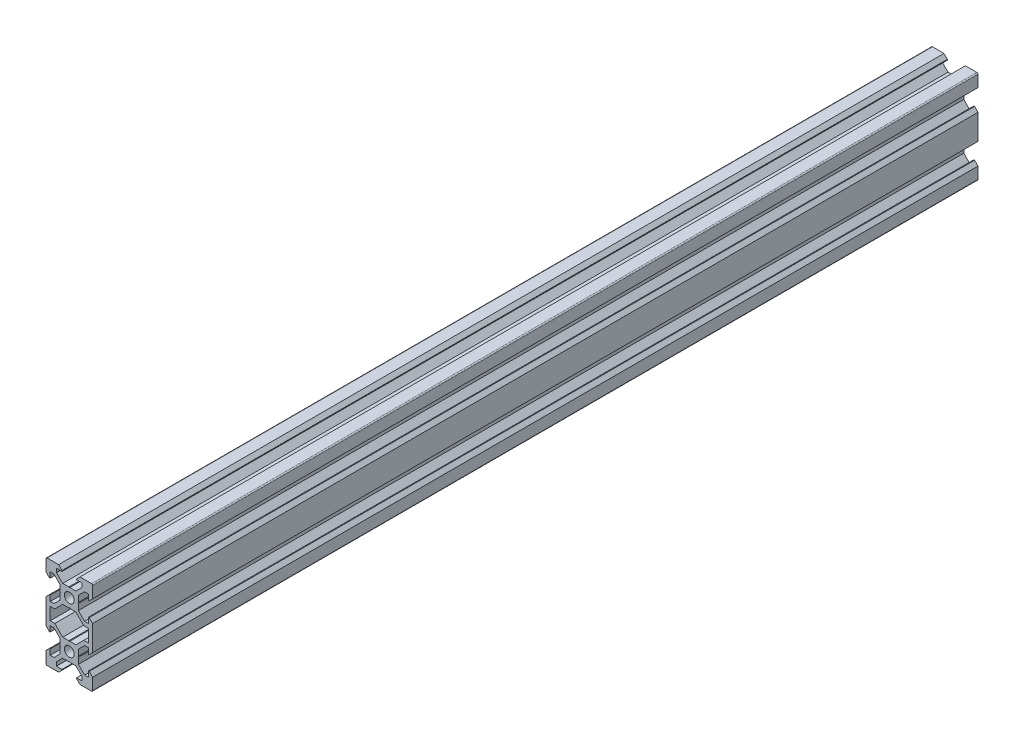
SolidWorks part; units mm, degrees
ref_plane "Plan de face" through (0, 0, 0) normal (0, 0, 1) x (1, 0, 0)
ref_plane "Plan de dessus" through (0, 0, 0) normal (0, 1, 0) x (1, 0, 0)
ref_plane "Plan de droite" through (0, 0, 0) normal (1, 0, 0) x (0, 0, -1)
ref_axis "Axe" through (0, 0, -13.782) along (0, 0, 1)
sketch "Esquisse1" plane through (0, 0, 0) normal (0, 0, 1) x (1, 0, 0)
  line L0 (0, 22.8977) -> (0, -22.8977) construction
  line L1 (-33.6074, 0) -> (33.6074, 0) construction
  line L2 (0, 0) -> (-22.2114, 22.2114) construction
  line L3 (-9.5, 10) -> (-4.58, 10)
  line L4 (-4.58, 10) -> (-3.125, 8.545)
  line L5 (-3.125, 8.545) -> (-3.125, 8.2)
  line L6 (-3.125, 8.2) -> (-5.5, 8.2)
  line L7 (-2.8393, 3.9) -> (-5.5, 6.5607)
  line L8 (-2.8393, 3.9) -> (-0.21, 3.9)
  line L9 (-5.5, 6.5607) -> (-5.5, 8.2)
  line L10 (0, 3.69) -> (0, 2.1)
  line L11 (-3.9, 2.8393) -> (-6.5607, 5.5)
  line L12 (-8.545, 3.125) -> (-8.2, 3.125)
  line L13 (-8.2, 3.125) -> (-8.2, 5.5)
  line L14 (-6.5607, 5.5) -> (-8.2, 5.5)
  line L15 (-10, 4.58) -> (-8.545, 3.125)
  line L16 (-10, 9.5) -> (-10, 4.58)
  line L17 (-0.21, 3.9) -> (0, 3.69)
  line L18 (-3.9, 2.8393) -> (-3.9, 0.21)
  line L20 (-3.9, 0.21) -> (-3.69, 0)
  line L21 (-0.21, -3.9) -> (0, -3.69)
  line L22 (0, -3.69) -> (0, -2.1)
  line L23 (-6.5607, -5.5) -> (-8.2, -5.5)
  line L24 (-2.8393, -3.9) -> (-0.21, -3.9)
  line L25 (-8.545, -3.125) -> (-8.2, -3.125)
  line L26 (-10, -4.58) -> (-8.545, -3.125)
  line L27 (-8.2, -3.125) -> (-8.2, -5.5)
  line L28 (-2.8393, -3.9) -> (-6.2393, -7.3)
  line L29 (-3.9, -2.8393) -> (-6.5607, -5.5)
  line L30 (-3.9, -2.8393) -> (-3.9, -0.21)
  line L31 (-3.9, -0.21) -> (-3.69, 0)
  line L32 (-6.2393, -7.3) -> (-8.2, -7.3)
  line L33 (-8.2, -7.3) -> (-8.2, -10)
  line L34 (-8.2, -10) -> (-10, -10)
  line L35 (-10, -10) -> (-10, -4.58)
  arc A0 (0, -2.1) -> (0, 2.1) centre (0, 0) cw
  arc A1 (-9.5, 10) -> (-10, 9.5) centre (-9.5, 9.5) ccw
  point P4 (0, 0)
  point P7 (0, 0)
  point P30 (-10, 10)
  dimension "D5" = 11
  dimension "D2" = 2.1
  dimension "D3" = 6.25
  dimension "D10" = 0.5
  dimension "D4" = 9.16
  dimension "D6" = 1.5
  dimension "D7" = 1.8
  dimension "D8" = 4.3
  dimension "D9" = 20
  dimension "D11" = 0.42
  dimension "D12" = 10
  dimension "D13" = 1.8
extrude "Boss.-Extru.1" add sketch "Esquisse1" along normal blind 380
sketch "Esquisse3" plane through (0, 0, 380) normal (0, 0, 1) x (1, 0, 0)
  line L0 (0, 0) -> (-9.8536, 9.8536) construction
  line L1 (-8.2, 8.2) -> (-8.2, 6.57)
  line L2 (-8.2, 6.57) -> (-7.54, 6.57)
  line L3 (-7.54, 6.57) -> (-6.57, 7.54)
  line L4 (-8.2, 3.125) -> (-8.2, 5.5) construction
  line L5 (-6.57, 8.2) -> (-6.57, 7.54)
  line L6 (-8.2, 8.2) -> (-6.57, 8.2)
  line L7 (-5.5, 6.5607) -> (-5.5, 8.2) construction
  arc A0 (-9.5, 10) -> (-10, 9.5) centre (-9.5, 9.5) ccw construction
  point P13 (-7.055, 7.055)
  point P14 (-6.57, 7.87)
  dimension "D1" = 1.07
extrude "Enlèv. mat.-Extru.1" [suppressed] cut sketch "Esquisse3" against normal through all
mirror "Symétrie1" about plane through (0, 3.69, 380) normal (-1, 0, 0) of "Enlèv. mat.-Extru.1", "Boss.-Extru.1"
mirror "Symétrie6" about plane through (-8.2, -10, 380) normal (0, 1, 0) of "Symétrie1", "Boss.-Extru.1"
